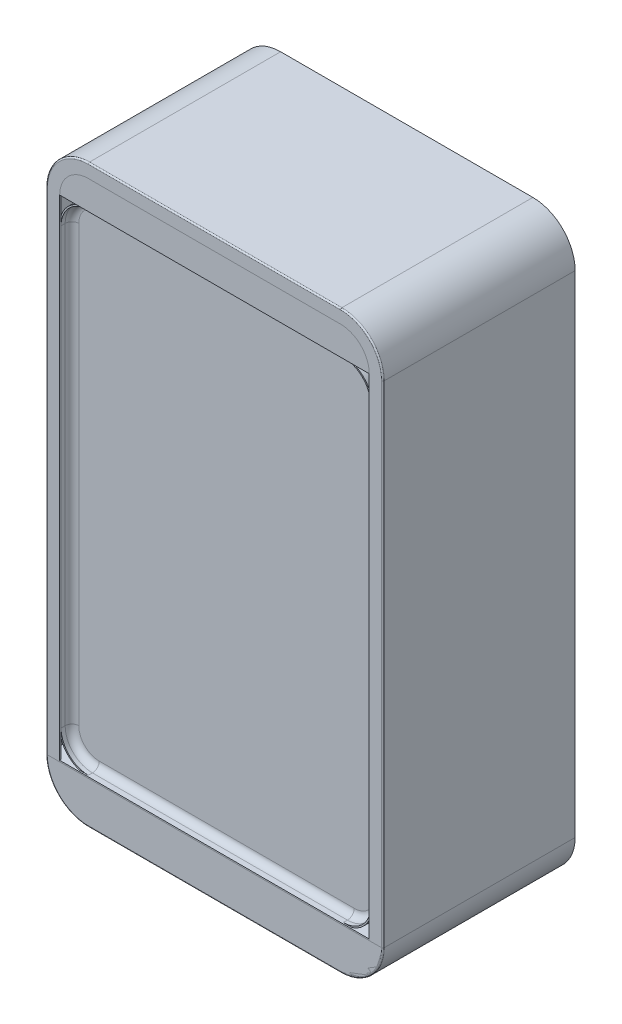
SolidWorks part; units mm, degrees
ref_plane "Front Plane" through (0, 0, 0) normal (0, 0, 1) x (1, 0, 0)
ref_plane "Top Plane" through (0, 0, 0) normal (0, 1, 0) x (1, 0, 0)
ref_plane "Right Plane" through (0, 0, 0) normal (1, 0, 0) x (0, 0, -1)
sketch "Sketch1" plane through (0, 0, 0) normal (0, 0, 1) x (1, 0, 0)
  line L0 (-234.95, 535.94) -> (234.95, 535.94)
  line L1 (-234.95, 533.4) -> (234.95, 533.4)
  line L2 (-311.15, 457.2) -> (-311.15, -457.2)
  line L3 (-234.95, -533.4) -> (234.95, -533.4)
  line L4 (311.15, 457.2) -> (311.15, -457.2)
  line L5 (-311.15, 533.4) -> (311.15, -533.4) construction
  line L6 (-311.15, -533.4) -> (311.15, 533.4) construction
  line L7 (313.69, 457.2) -> (313.69, -457.2)
  line L8 (-234.95, -535.94) -> (234.95, -535.94)
  line L9 (-313.69, 457.2) -> (-313.69, -457.2)
  arc A0 (-311.15, -457.2) -> (-234.95, -533.4) centre (-234.95, -457.2) ccw
  arc A1 (234.95, -533.4) -> (311.15, -457.2) centre (234.95, -457.2) ccw
  arc A2 (234.95, 533.4) -> (311.15, 457.2) centre (234.95, 457.2) cw
  arc A3 (-234.95, 533.4) -> (-311.15, 457.2) centre (-234.95, 457.2) ccw
  arc A4 (234.95, 535.94) -> (313.69, 457.2) centre (234.95, 457.2) cw
  arc A5 (234.95, -535.94) -> (313.69, -457.2) centre (234.95, -457.2) ccw
  arc A6 (-313.69, -457.2) -> (-234.95, -535.94) centre (-234.95, -457.2) ccw
  arc A7 (-234.95, 535.94) -> (-313.69, 457.2) centre (-234.95, 457.2) ccw
  point P0 (0, 0)
  dimension "D3" = 76.2
  dimension "D1" = 622.3
  dimension "D2" = 1066.8
  dimension "D4" = 2.54
extrude "Boss-Extrude1" add sketch "Sketch1" along normal blind 355.6
sketch "Sketch2" plane through (0, 0, 355.6) normal (0, 0, 1) x (1, 0, 0)
  line L0 (-288.29, 457.2) -> (-288.29, -457.2)
  line L1 (-234.95, -510.54) -> (234.95, -510.54)
  line L2 (288.29, -457.2) -> (288.29, 457.2)
  line L3 (234.95, 510.54) -> (-234.95, 510.54)
  line L4 (-313.69, 457.2) -> (-313.69, -457.2)
  line L5 (-234.95, -535.94) -> (234.95, -535.94)
  line L6 (313.69, -457.2) -> (313.69, 457.2)
  line L7 (234.95, 535.94) -> (-234.95, 535.94)
  line L8 (-313.69, 457.2) -> (-313.69, -457.2)
  line L9 (-234.95, -535.94) -> (234.95, -535.94)
  line L10 (313.69, -457.2) -> (313.69, 457.2)
  line L11 (234.95, 535.94) -> (-234.95, 535.94)
  arc A0 (-234.95, 510.54) -> (-288.29, 457.2) centre (-234.95, 457.2) ccw
  arc A1 (-288.29, -457.2) -> (-234.95, -510.54) centre (-234.95, -457.2) ccw
  arc A2 (234.95, -510.54) -> (288.29, -457.2) centre (234.95, -457.2) ccw
  arc A3 (288.29, 457.2) -> (234.95, 510.54) centre (234.95, 457.2) ccw
  arc A4 (-234.95, 535.94) -> (-313.69, 457.2) centre (-234.95, 457.2) ccw
  arc A5 (-313.69, -457.2) -> (-234.95, -535.94) centre (-234.95, -457.2) ccw
  arc A6 (234.95, -535.94) -> (313.69, -457.2) centre (234.95, -457.2) ccw
  arc A7 (313.69, 457.2) -> (234.95, 535.94) centre (234.95, 457.2) ccw
  arc A8 (-234.95, 535.94) -> (-313.69, 457.2) centre (-234.95, 457.2) ccw
  arc A9 (-313.69, -457.2) -> (-234.95, -535.94) centre (-234.95, -457.2) ccw
  arc A10 (234.95, -535.94) -> (313.69, -457.2) centre (234.95, -457.2) ccw
  arc A11 (313.69, 457.2) -> (234.95, 535.94) centre (234.95, 457.2) ccw
  dimension "D1" = 0
  dimension "D2" = 25.4
extrude "Boss-Extrude2" add sketch "Sketch2" along normal blind 2.54 separate body
fillet "Fillet1" radius 2.54 8 edges at (313.69, 0, 358.14) (290.6276, -512.8776, 358.14) (0, -535.94, 358.14) (-290.6276, -512.8776, 358.14) (-313.69, 0, 358.14) (-290.6276, 512.8776, 358.14) (0, 535.94, 358.14) (290.6276, 512.8776, 358.14)
sketch "Sketch3" plane through (311.15, 0, 0) normal (-1, 0, 0) x (0, 0, 1)
  line L0 (0, -457.2) -> (0, 457.2) construction
  line L1 (358.14, -457.2) -> (0, -457.2)
  line L2 (358.14, -457.2) -> (358.14, -454.66)
  line L3 (358.14, -454.66) -> (0, -454.66)
  line L4 (0, -457.2) -> (0, -454.66)
  dimension "D1" = 2.54
extrude "Boss-Extrude3" add sketch "Sketch3" along normal up to surface (622.3 mm away) separate body up to face at (-311.15, 0, 177.8)
sketch "Sketch4" plane through (0, 0, 0) normal (0, 0, -1) x (-1, 0, 0)
  line L0 (311.15, -457.2) -> (-311.15, -457.2) construction
  line L1 (234.95, -533.4) -> (-234.95, -533.4) construction
  line L2 (311.15, -457.2) -> (-311.15, -457.2)
  line L3 (234.95, -533.4) -> (-234.95, -533.4)
  arc A0 (-311.15, -457.2) -> (-234.95, -533.4) centre (-234.95, -457.2) ccw construction
  arc A1 (234.95, -533.4) -> (311.15, -457.2) centre (234.95, -457.2) ccw construction
  arc A2 (-311.15, -457.2) -> (-234.95, -533.4) centre (-234.95, -457.2) ccw
  arc A3 (234.95, -533.4) -> (311.15, -457.2) centre (234.95, -457.2) ccw
extrude "Boss-Extrude4" add sketch "Sketch4" against normal blind 2.54 separate body
sketch "Sketch5" plane through (0, 0, 0) normal (0, 0, -1) x (-1, 0, 0)
  line L1 (-311.15, -454.66) -> (311.15, -454.66)
  line L2 (-311.15, -454.66) -> (-311.15, 167.64)
  line L3 (-311.15, 167.64) -> (311.15, 167.64)
  line L4 (311.15, -454.66) -> (311.15, 167.64)
  line L5 (-285.75, 142.24) -> (285.75, 142.24)
  line L6 (285.75, -429.26) -> (285.75, 142.24)
  line L7 (-285.75, -429.26) -> (285.75, -429.26)
  line L8 (-285.75, -429.26) -> (-285.75, 142.24)
  dimension "D1" = 622.3
  dimension "D2" = 25.4
extrude "Boss-Extrude5" add sketch "Sketch5" along normal blind 2.54 from offset 273.05 separate body offset against normal yes
sketch "Sketch6" plane through (0, 0, 270.51) normal (0, 0, -1) x (-1, 0, 0)
  line L0 (-311.15, 167.64) -> (-285.75, 167.64)
  line L1 (311.15, 167.64) -> (-311.15, 167.64) construction
  line L2 (-311.15, 167.64) -> (-311.15, 142.24)
  line L3 (-311.15, 167.64) -> (-311.15, -454.66) construction
  line L4 (285.75, 167.64) -> (311.15, 167.64)
  line L5 (311.15, 167.64) -> (311.15, 142.24)
  line L6 (311.15, -454.66) -> (311.15, 167.64) construction
  line L7 (285.75, 167.64) -> (285.75, 165.1)
  line L8 (285.75, 165.1) -> (308.61, 165.1)
  line L9 (308.61, 165.1) -> (308.61, 142.24)
  line L10 (308.61, 142.24) -> (311.15, 142.24)
  line L11 (-311.15, 142.24) -> (-308.61, 142.24)
  line L12 (-308.61, 142.24) -> (-308.61, 165.1)
  line L13 (-308.61, 165.1) -> (-285.75, 165.1)
  line L14 (-285.75, 165.1) -> (-285.75, 167.64)
  line L15 (-285.75, -143.51) -> (285.75, -143.51) construction
  line L16 (-285.75, 142.24) -> (-285.75, -429.26) construction
  line L17 (285.75, -429.26) -> (285.75, 142.24) construction
  line L18 (-285.75, -452.12) -> (-285.75, -454.66)
  line L19 (-308.61, -452.12) -> (-285.75, -452.12)
  line L20 (-308.61, -429.26) -> (-308.61, -452.12)
  line L21 (-311.15, -429.26) -> (-308.61, -429.26)
  line L22 (308.61, -429.26) -> (311.15, -429.26)
  line L23 (308.61, -452.12) -> (308.61, -429.26)
  line L24 (285.75, -452.12) -> (308.61, -452.12)
  line L25 (285.75, -454.66) -> (285.75, -452.12)
  line L26 (311.15, -454.66) -> (311.15, -429.26)
  line L27 (285.75, -454.66) -> (311.15, -454.66)
  line L28 (-311.15, -454.66) -> (-311.15, -429.26)
  line L29 (-311.15, -454.66) -> (-285.75, -454.66)
  dimension "D1" = 25.4
  dimension "D2" = 25.4
  dimension "D3" = 25.4
  dimension "D4" = 25.4
  dimension "D5" = 2.54
  dimension "D6" = 2.54
  dimension "D7" = 2.54
  dimension "D8" = 2.54
sketch "Sketch8" plane through (0, 0, 358.14) normal (0, 0, 1) x (1, 0, 0)
  line L0 (-311.15, -457.2) -> (311.15, -457.2) construction
  line L1 (-234.95, -533.4) -> (234.95, -533.4) construction
  line L2 (-311.15, -457.2) -> (311.15, -457.2)
  line L3 (-234.95, -533.4) -> (234.95, -533.4)
  arc A0 (-311.15, -457.2) -> (-234.95, -533.4) centre (-234.95, -457.2) ccw construction
  arc A1 (234.95, -533.4) -> (311.15, -457.2) centre (234.95, -457.2) ccw construction
  arc A2 (-311.15, -457.2) -> (-234.95, -533.4) centre (-234.95, -457.2) ccw
  arc A3 (234.95, -533.4) -> (311.15, -457.2) centre (234.95, -457.2) ccw
extrude "Boss-Extrude6" add sketch "Sketch8" against normal blind 2.54 separate body
extrude "Boss-Extrude7" add sketch "Sketch6" along normal up to surface (270.51 mm away) up to face at (0, 0, 0)
sketch "Sketch9" plane through (0, 167.64, 0) normal (0, 1, 0) x (1, 0, 0)
  line L0 (285.75, 0) -> (285.75, -270.51) construction
  line L1 (-285.75, -270.51) -> (285.75, -270.51)
  line L2 (-285.75, -270.51) -> (-285.75, -245.11)
  line L3 (-285.75, -245.11) -> (285.75, -245.11)
  line L4 (285.75, -270.51) -> (285.75, -245.11)
  dimension "D1" = 25.4
extrude "Boss-Extrude8" add sketch "Sketch9" against normal blind 2.54
sketch "Sketch10" plane through (0, 167.64, 0) normal (0, 1, 0) x (1, 0, 0)
  line L1 (311.15, 0) -> (-311.15, 0)
  line L2 (311.15, 0) -> (311.15, -273.05)
  line L3 (311.15, -273.05) -> (-311.15, -273.05)
  line L4 (-311.15, 0) -> (-311.15, -273.05)
extrude "Boss-Extrude9" add sketch "Sketch10" along normal blind 2.54 separate body
sketch "Sketch11" plane through (0, 0, 358.14) normal (0, 0, 1) x (1, 0, 0)
  line L0 (234.95, 510.54) -> (-234.95, 510.54) construction
  line L1 (234.95, 510.54) -> (-234.95, 510.54)
  line L2 (-288.29, 457.2) -> (288.29, 457.2)
  arc A0 (-234.95, 510.54) -> (-288.29, 457.2) centre (-234.95, 457.2) ccw construction
  arc A1 (288.29, 457.2) -> (234.95, 510.54) centre (234.95, 457.2) ccw construction
  arc A2 (-234.95, 510.54) -> (-288.29, 457.2) centre (-234.95, 457.2) ccw
  arc A3 (288.29, 457.2) -> (234.95, 510.54) centre (234.95, 457.2) ccw
extrude "Boss-Extrude10" add sketch "Sketch11" against normal blind 2.54 separate body
fillet "Fillet2" radius 50.8 rebuild error yes
fillet "Fillet3" radius 50.8 rebuild error yes
sketch "Sketch12" plane through (0, 0, 358.14) normal (0, 0, 1) x (1, 0, 0)
  line L0 (-237.49, 457.2) -> (237.49, 457.2) construction
  line L1 (288.29, -403.86) -> (288.29, 406.4) construction
  line L2 (-237.49, -454.66) -> (237.49, -454.66) construction
  line L3 (-288.29, 406.4) -> (-288.29, -403.86) construction
  line L4 (-237.49, 457.2) -> (237.49, 457.2)
  line L5 (288.29, -403.86) -> (288.29, 406.4)
  line L6 (-237.49, -454.66) -> (237.49, -454.66)
  line L7 (-288.29, 406.4) -> (-288.29, -403.86)
  arc A0 (-237.49, 457.2) -> (-288.29, 406.4) centre (-237.49, 406.4) ccw construction
  arc A1 (288.29, 406.4) -> (237.49, 457.2) centre (237.49, 406.4) ccw construction
  arc A2 (237.49, -454.66) -> (288.29, -403.86) centre (237.49, -403.86) ccw construction
  arc A3 (-288.29, -403.86) -> (-237.49, -454.66) centre (-237.49, -403.86) ccw construction
  arc A4 (-237.49, 457.2) -> (-288.29, 406.4) centre (-237.49, 406.4) ccw
  arc A5 (288.29, 406.4) -> (237.49, 457.2) centre (237.49, 406.4) ccw
  arc A6 (237.49, -454.66) -> (288.29, -403.86) centre (237.49, -403.86) ccw
  arc A7 (-288.29, -403.86) -> (-237.49, -454.66) centre (-237.49, -403.86) ccw
extrude "Boss-Extrude11" add sketch "Sketch12" along normal blind 2.54 from offset 25.4 separate body offset against normal yes
fillet "Fillet4" radius 2.54 rebuild error yes
sketch "Sketch13" plane through (0, 0, 332.74) normal (0, 0, -1) x (-1, 0, 0)
  line L0 (237.49, 459.74) -> (-237.49, 459.74)
  line L1 (-290.83, 406.4) -> (-290.83, -403.86)
  line L2 (-237.49, -457.2) -> (237.49, -457.2)
  line L3 (290.83, -403.86) -> (290.83, 406.4)
  line L4 (237.49, 457.2) -> (-237.49, 457.2)
  line L5 (-288.29, 406.4) -> (-288.29, -403.86)
  line L6 (-237.49, -454.66) -> (237.49, -454.66)
  line L7 (288.29, -403.86) -> (288.29, 406.4)
  line L8 (237.49, 457.2) -> (-237.49, 457.2)
  line L9 (-288.29, 406.4) -> (-288.29, -403.86)
  line L10 (-237.49, -454.66) -> (237.49, -454.66)
  line L11 (288.29, -403.86) -> (288.29, 406.4)
  arc A0 (-237.49, 459.74) -> (-290.83, 406.4) centre (-237.49, 406.4) ccw
  arc A1 (-290.83, -403.86) -> (-237.49, -457.2) centre (-237.49, -403.86) ccw
  arc A2 (237.49, -457.2) -> (290.83, -403.86) centre (237.49, -403.86) ccw
  arc A3 (290.83, 406.4) -> (237.49, 459.74) centre (237.49, 406.4) ccw
  arc A4 (288.29, 406.4) -> (237.49, 457.2) centre (237.49, 406.4) ccw
  arc A5 (-237.49, 457.2) -> (-288.29, 406.4) centre (-237.49, 406.4) ccw
  arc A6 (-288.29, -403.86) -> (-237.49, -454.66) centre (-237.49, -403.86) ccw
  arc A7 (237.49, -454.66) -> (288.29, -403.86) centre (237.49, -403.86) ccw
  arc A8 (288.29, 406.4) -> (237.49, 457.2) centre (237.49, 406.4) ccw
  arc A9 (-237.49, 457.2) -> (-288.29, 406.4) centre (-237.49, 406.4) ccw
  arc A10 (-288.29, -403.86) -> (-237.49, -454.66) centre (-237.49, -403.86) ccw
  arc A11 (237.49, -454.66) -> (288.29, -403.86) centre (237.49, -403.86) ccw
  dimension "D1" = 0
  dimension "D2" = 2.54
extrude "Boss-Extrude12" add sketch "Sketch13" against normal up to surface (22.86 mm away) up to face at (0, 0, 355.6)
fillet "Fillet5" radius 12.7 8 edges at (273.411, -439.781, 335.28) (0, -454.66, 335.28) (-273.411, -439.781, 335.28) (-288.29, 1.27, 335.28) (-273.411, 442.321, 335.28) (0, 457.2, 335.28) (273.411, 442.321, 335.28) (288.29, 1.27, 335.28)
